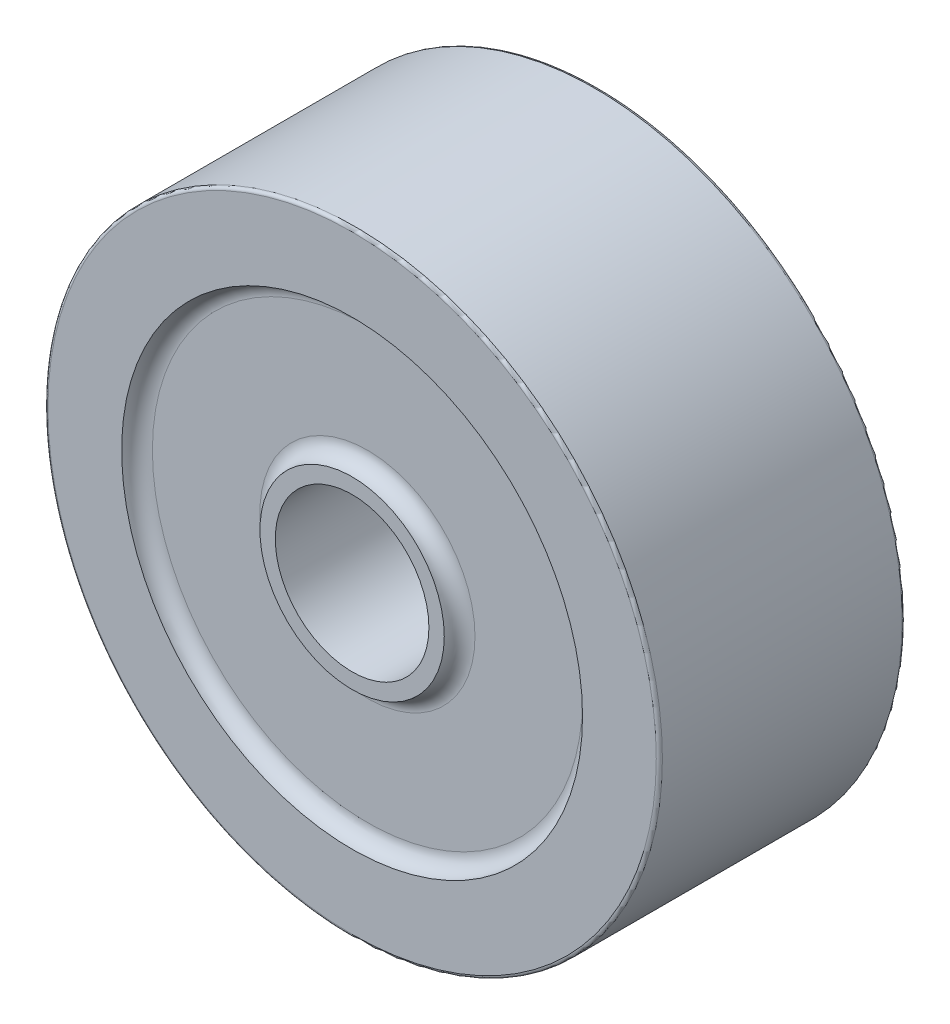
SolidWorks part; units mm, degrees
ref_plane "Front Plane" through (0, 0, 0) normal (0, 0, 1) x (1, 0, 0)
ref_plane "Top Plane" through (0, 0, 0) normal (0, 1, 0) x (1, 0, 0)
ref_plane "Right Plane" through (0, 0, 0) normal (1, 0, 0) x (0, 0, -1)
sketch "Sketch2" plane through (0, 0, 0) normal (1, 0, 0) x (0, 0, -1)
  line L0 (0, -7.62) -> (1.27, -7.62)
  line L1 (0, 0) -> (20.32, 0)
  line L2 (0, 0) -> (0, -7.62)
  line L3 (0, -25.4) -> (20.32, -25.4)
  line L4 (20.32, 0) -> (20.32, -11.43)
  line L5 (1.27, -7.62) -> (1.27, -19.05)
  line L6 (1.27, -19.05) -> (0, -19.05)
  line L7 (0, -19.05) -> (0, -25.4)
  line L8 (10.16, 0) -> (10.16, -25.4) construction
  line L9 (20.32, -11.43) -> (19.05, -11.43)
  line L10 (19.05, -11.43) -> (19.05, -19.05)
  line L11 (19.05, -19.05) -> (20.32, -19.05)
  line L12 (20.32, -19.05) -> (20.32, -25.4)
  dimension "D1" = 25.4
  dimension "D2" = 7.62
  dimension "D3" = 6.35
  dimension "D4" = 1.27
  dimension "D5" = 20.32
  dimension "D6" = 11.43
revolve "Revolve1" add sketch "Sketch2" angle 360 about L1
sketch "Sketch3" plane through (0, 0, 0) normal (0, 0, 1) x (1, 0, 0)
  circle A0 centre (0, 0) radius 6.35
  dimension "D1" = 12.7
extrude "Cut-Extrude1" cut sketch "Sketch3" against normal through all contours A0
fillet "Fillet1" radius 1.27 4 edges at (11.43, 0, -19.05) (19.05, 0, -19.05) (7.62, 0, -1.27) (19.05, 0, -1.27)
fillet "Fillet2" radius 0.254 2 edges at (25.4, 0, 0) (25.4, 0, -20.32)
sketch "Sketch4" plane through (0, 0, -20.32) normal (0, 0, -1) x (-1, 0, 0)
  line L1 (-6.35, -6.35) -> (6.35, -6.35)
  line L2 (-6.35, -6.35) -> (-6.35, 6.35)
  line L3 (-6.35, 6.35) -> (6.35, 6.35)
  line L4 (6.35, -6.35) -> (6.35, 6.35)
  circle A1 centre (0, 0) radius 6.35 construction
extrude "Cut-Extrude2" cut sketch "Sketch4" against normal blind 5.08
